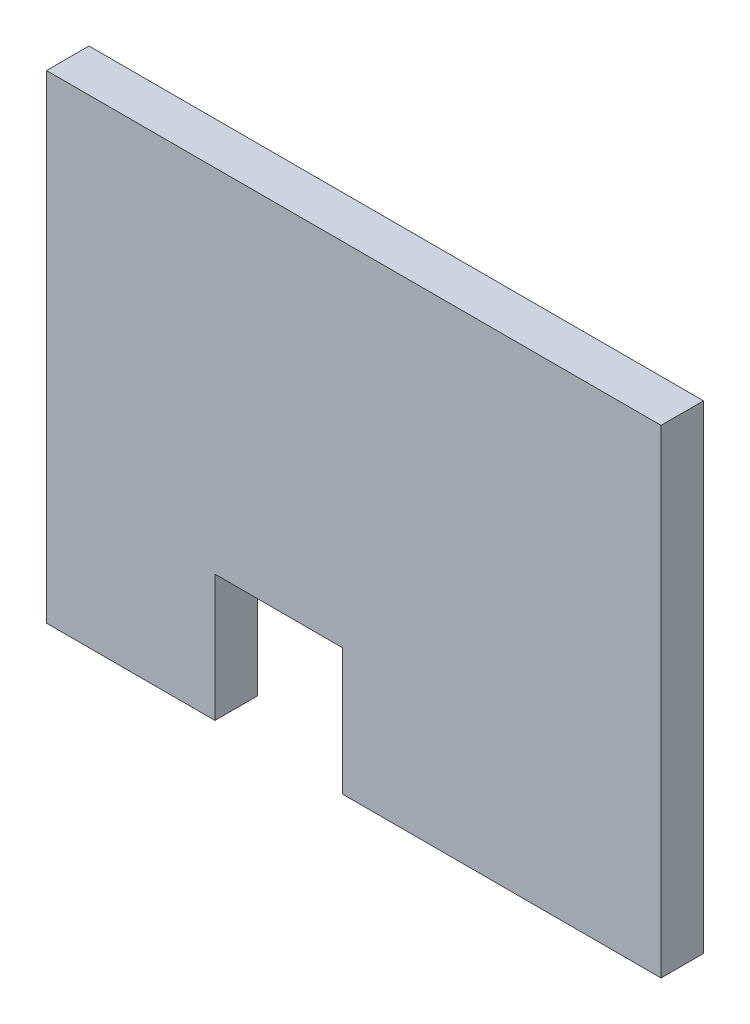
SolidWorks part; units mm, degrees
ref_plane "Front Plane" through (0, 0, 0) normal (0, 0, 1) x (1, 0, 0)
ref_plane "Top Plane" through (0, 0, 0) normal (0, 1, 0) x (1, 0, 0)
ref_plane "Right Plane" through (0, 0, 0) normal (1, 0, 0) x (0, 0, -1)
sketch "Sketch1" plane through (0, 0, 0) normal (0, 0, 1) x (1, 0, 0)
  line L0 (21.7, 44.25) -> (21.7, 15.05) construction
  line L1 (21.7, 48.85) -> (-21.7, 48.85)
  line L2 (21.7, 48.85) -> (21.7, 15.05)
  line L3 (21.7, 15.05) -> (-0.8, 15.05)
  line L4 (-21.7, 48.85) -> (-21.7, 15.05)
  line L5 (-21.7, 44.25) -> (-21.7, 15.05) construction
  line L6 (32.157, 48.85) -> (-32.157, 48.85) construction
  line L7 (28.7, 15.05) -> (-28.7, 15.05) construction
  line L8 (-0.8, 15.05) -> (-0.8, 24) construction
  line L9 (-0.8, 24) -> (-9.8, 24) construction
  line L10 (-9.8, 24) -> (-9.8, 15.05) construction
  line L11 (-0.8, 15.05) -> (-0.8, 24)
  line L12 (-0.8, 24) -> (-9.8, 24)
  line L13 (-9.8, 24) -> (-9.8, 15.05)
  line L14 (-9.8, 15.05) -> (-21.7, 15.05)
sketch "Sketch2" plane through (0, 0, 0) normal (1, 0, 0) x (0, 0, -1)
  line L0 (0, 19.65) -> (0, 48.85) construction
  line L1 (0, 48.85) -> (-3, 48.85)
  line L2 (0, 48.85) -> (0, 15.05)
  line L3 (0, 15.05) -> (-3, 15.05)
  line L4 (-3, 48.85) -> (-3, 15.05)
  line L5 (-3, 19.65) -> (-3, 45.85) construction
  line L6 (-53.857, 15.05) -> (10.457, 15.05) construction
  line L7 (-50.4, 48.85) -> (7, 48.85) construction
extrude "Boss-Extrude1" add sketch "Sketch1" along normal up to vertex (3 mm away) up to point (0, 48.85, 3)
